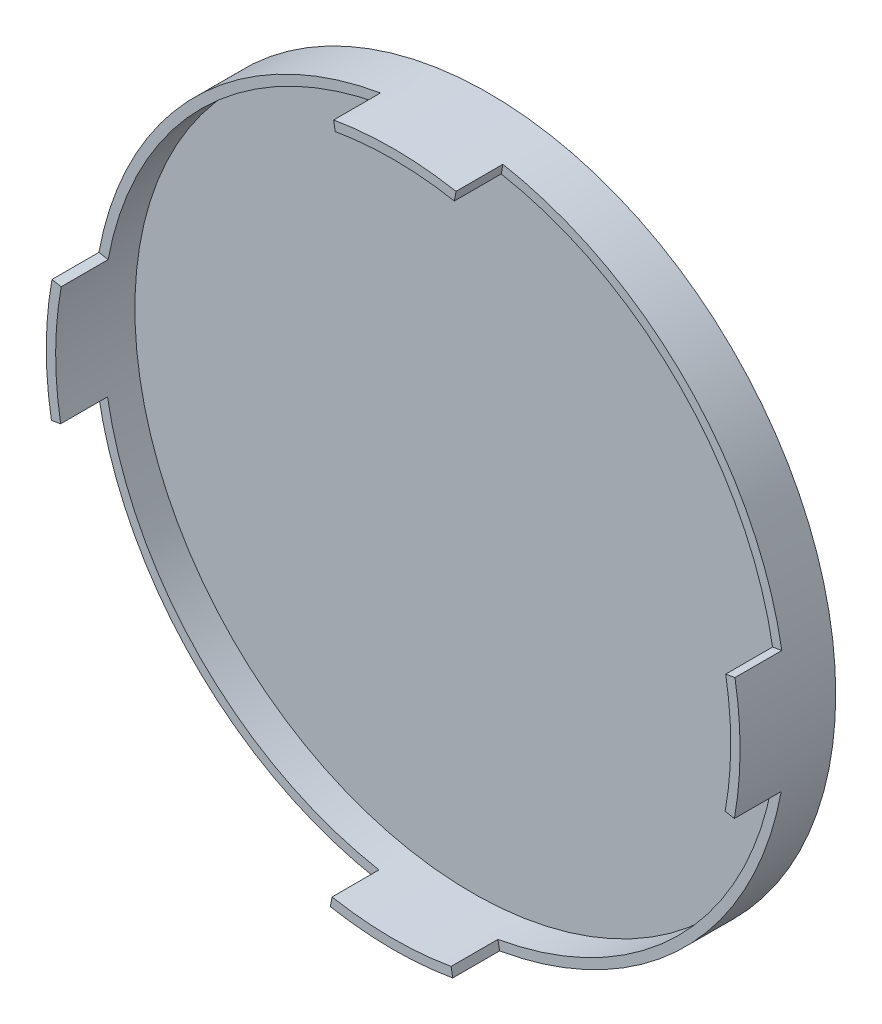
SolidWorks part; units mm, degrees
ref_plane "Front Plane" through (0, 0, 0) normal (0, 0, 1) x (1, 0, 0)
ref_plane "Top Plane" through (0, 0, 0) normal (0, 1, 0) x (1, 0, 0)
ref_plane "Right Plane" through (0, 0, 0) normal (1, 0, 0) x (0, 0, -1)
sketch "Sketch1" plane through (0, 0, 0) normal (0, 0, 1) x (1, 0, 0)
  circle A0 centre (0, 0) radius 74
  dimension "D1" = 148
extrude "Boss-Extrude1" add sketch "Sketch1" along normal blind 3.5
sketch "Sketch2" plane through (0, 0, 0) normal (0, 0, 1) x (1, 0, 0)
  circle A0 centre (0, 0) radius 26
  circle A1 centre (0, 0) radius 27
  circle A2 centre (0, 0) radius 15
  circle A3 centre (0, 0) radius 16
  circle A4 centre (0, 0) radius 37
  circle A5 centre (0, 0) radius 38
  circle A6 centre (0, 0) radius 48
  circle A7 centre (0, 0) radius 49
  circle A8 centre (0, 0) radius 59
  circle A9 centre (0, 0) radius 60
  dimension "D1" = 1
  dimension "D2" = 1
  dimension "D3" = 10
  dimension "D4" = 10
  dimension "D5" = 10
  dimension "D6" = 1
  dimension "D7" = 1
  dimension "D8" = 10
  dimension "D9" = 1
sketch "Sketch3" plane through (0, 0, 0) normal (0, 0, 1) x (1, 0, 0)
  circle A0 centre (0, 0) radius 74
  circle A1 centre (0, 0) radius 72
  dimension "D1" = 148
  dimension "D2" = 2
extrude "Boss-Extrude2" add sketch "Sketch3" along normal blind 10.4
sketch "Sketch5" plane through (0, 0, 10.4) normal (0, 0, 1) x (1, 0, 0)
  line L0 (0, 0) -> (-12.3541, 70.9322) construction
  line L1 (-12.3541, 70.9322) -> (-12.6973, 72.9025)
  line L2 (0, 0) -> (13.0459, 70.8082) construction
  line L3 (13.0459, 70.8082) -> (13.4083, 72.7751)
  circle A0 centre (0, 0) radius 74 construction
  circle A1 centre (0, 0) radius 72 construction
  arc A2 (-12.3541, 70.9322) -> (13.0459, 70.8082) centre (0, 0) cw
  circle A3 centre (0, 0) radius 72 construction
  arc A4 (13.4083, 72.7751) -> (-12.6973, 72.9025) centre (0, 0) ccw
  dimension "D1" = 25.4
extrude "Boss-Extrude3" add sketch "Sketch5" along normal blind 10
pattern_circular "CirPattern1" count 4 over 360 about axis through (0, 0, 3.5) along (0, 0, 1) of "Boss-Extrude3"
extrude "Cut-Extrude1" cut sketch "Sketch2" along normal blind 1 contours A3 | A2
extrude "Cut-Extrude2" cut sketch "Sketch2<3>" along normal blind 1 contours A1 | A0
sketch "Sketch2<3>" plane through (0, 0, 0) normal (0, 0, 1) x (1, 0, 0) same geometry as "Sketch2"
extrude "Cut-Extrude3" cut sketch "Sketch2<4>" along normal blind 1 contours A5 | A4
sketch "Sketch2<4>" plane through (0, 0, 0) normal (0, 0, 1) x (1, 0, 0) same geometry as "Sketch2"
extrude "Cut-Extrude4" cut sketch "Sketch2<5>" along normal blind 1 contours A7 | A6
sketch "Sketch2<5>" plane through (0, 0, 0) normal (0, 0, 1) x (1, 0, 0) same geometry as "Sketch2"
extrude "Cut-Extrude5" cut sketch "Sketch2<6>" along normal blind 1 contours A9 | A8
sketch "Sketch2<6>" plane through (0, 0, 0) normal (0, 0, 1) x (1, 0, 0) same geometry as "Sketch2"
fillet "Fillet1" radius 0.5 10 edges at (15, 0, 0) (16, 0, 1) (26, 0, 0) (27, 0, 0) (37, 0, 0) (38, 0, 0) (48, 0, 0) (49, 0, 0) (59, 0, 0) (60, 0, 0)
